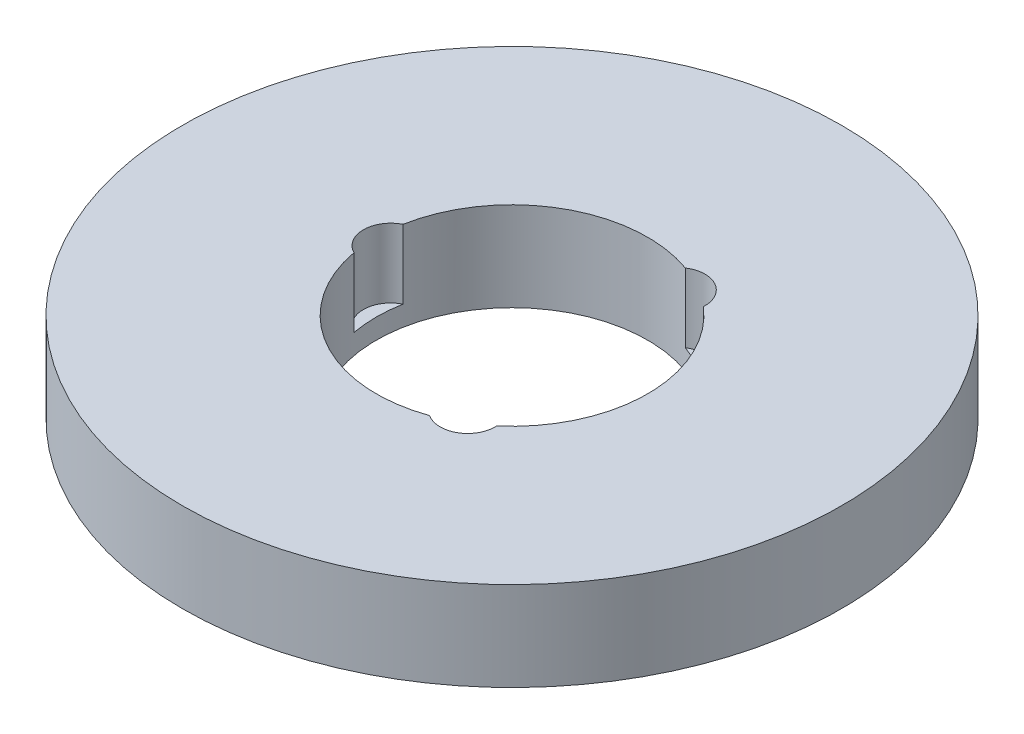
SolidWorks part; units mm, degrees
ref_plane "Front Plane" through (0, 0, 0) normal (0, 0, 1) x (1, 0, 0)
ref_plane "Top Plane" through (0, 0, 0) normal (0, 1, 0) x (1, 0, 0)
ref_plane "Right Plane" through (0, 0, 0) normal (1, 0, 0) x (0, 0, -1)
sketch "Sketch1" plane through (0, 0, 0) normal (0, 1, 0) x (1, 0, 0)
  circle A0 centre (0, 0) radius 85
  dimension "FLANGE_OD" = 170
extrude "Boss-Extrude1" add sketch "Sketch1" along normal blind 23
sketch "Sketch2" plane through (0, 0, 0) normal (0, 1, 0) x (1, 0, 0)
  circle A0 centre (0, 0) radius 35
  dimension "BORE_D" = 70
extrude "Cut-Extrude1" cut sketch "Sketch2" along normal through all
sketch "Sketch3" plane through (0, 23, 0) normal (0, 1, 0) x (1, 0, 0)
  circle A0 centre (0, 0) radius 31.2551 construction
  circle A1 centre (-31.2551, 0) radius 7.0774
  dimension "BOLT_D" = 14.1548
  dimension "BOLT_PCD" = 62.5103
extrude "Cut-Extrude2" cut sketch "Sketch3" against normal blind 17.8288
pattern_circular "CirPattern1" count 3 over 360 about axis through (0, 0, 0) along (0, 1, 0) of "Cut-Extrude2"
